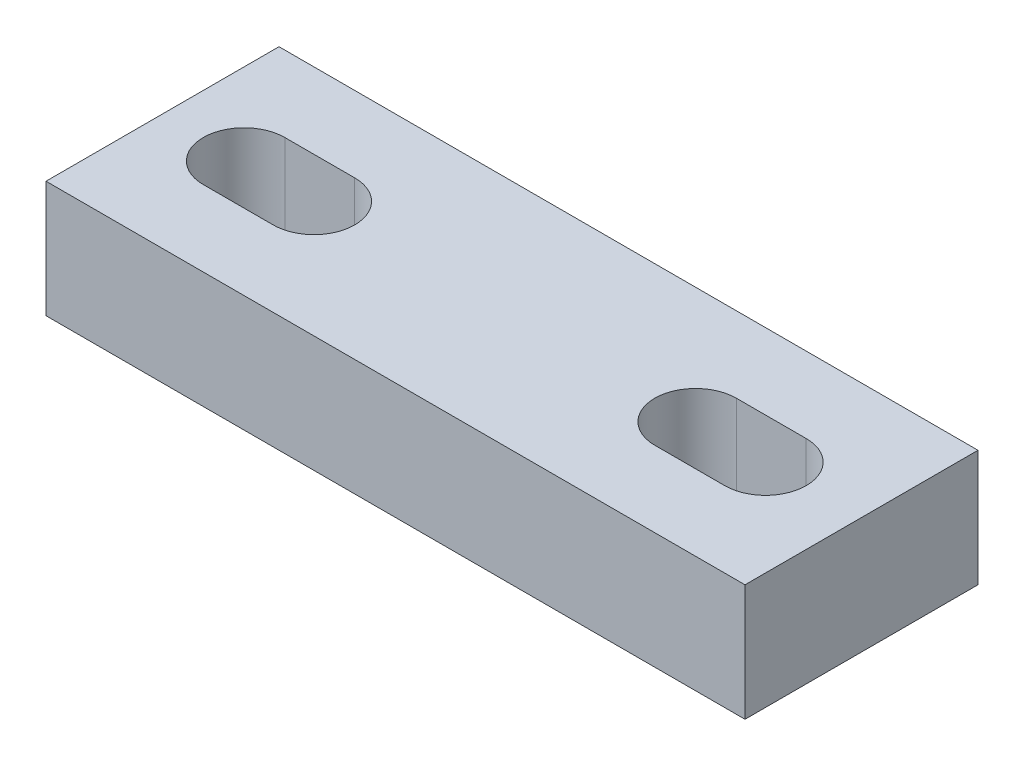
SolidWorks part; units mm, degrees
material "Lega 1060"
ref_plane "Piano frontale" through (0, 0, 0) normal (0, 0, 1) x (1, 0, 0)
ref_plane "Piano superiore" through (0, 0, 0) normal (0, 1, 0) x (1, 0, 0)
ref_plane "Piano destro" through (0, 0, 0) normal (1, 0, 0) x (0, 0, -1)
sketch "Schizzo1" plane through (0, 0, 0) normal (0, 0, 1) x (1, 0, 0)
  line L4 (-15, 0) -> (15, 0)
  line L5 (0, -4.2112) -> (0, 9.1781) construction
  line L7 (15, 0) -> (15, 5)
  line L8 (15, 5) -> (-15, 5)
  line L9 (-15, 5) -> (-15, 0)
  dimension "D1" = 5
  dimension "D4" = 30
extrude "Estrusione-Estrusione1" add sketch "Schizzo1" along normal blind 10
sketch "Schizzo2" plane through (0, 5, 0) normal (0, 1, 0) x (1, 0, 0)
  line L0 (-12.7999, -5) -> (12.1785, -5) construction
  line L1 (15, -10) -> (-15, -10) construction
  line L2 (15, 0) -> (-15, 0) construction
  line L3 (-15, -10) -> (-15, 0) construction
  line L4 (15, -10) -> (15, 0) construction
  line L5 (-11.5, -5) -> (-8.5, -5) construction
  line L6 (-11.5, -3.25) -> (-8.5, -3.25)
  line L7 (-11.5, -6.75) -> (-8.5, -6.75)
  line L8 (-0.3107, -5) -> (-0.3107, 0) construction
  line L9 (10.8786, -5) -> (7.8786, -5) construction
  line L10 (10.8786, -3.25) -> (7.8786, -3.25)
  line L11 (10.8786, -6.75) -> (7.8786, -6.75)
  arc A0 (-11.5, -3.25) -> (-11.5, -6.75) centre (-11.5, -5) ccw
  arc A1 (-8.5, -6.75) -> (-8.5, -3.25) centre (-8.5, -5) ccw
  arc A2 (10.8786, -3.25) -> (10.8786, -6.75) centre (10.8786, -5) cw
  arc A3 (7.8786, -6.75) -> (7.8786, -3.25) centre (7.8786, -5) cw
  point P0 (-10, -5)
  point P1 (10, -5)
  point P14 (-10, -5)
  point P23 (9.3786, -5)
  dimension "D4" = 3
  dimension "D1" = 5
  dimension "D2" = 5
  dimension "D3" = 3.5
extrude "Taglio-Estrusione1" cut sketch "Schizzo2" against normal blind 10
